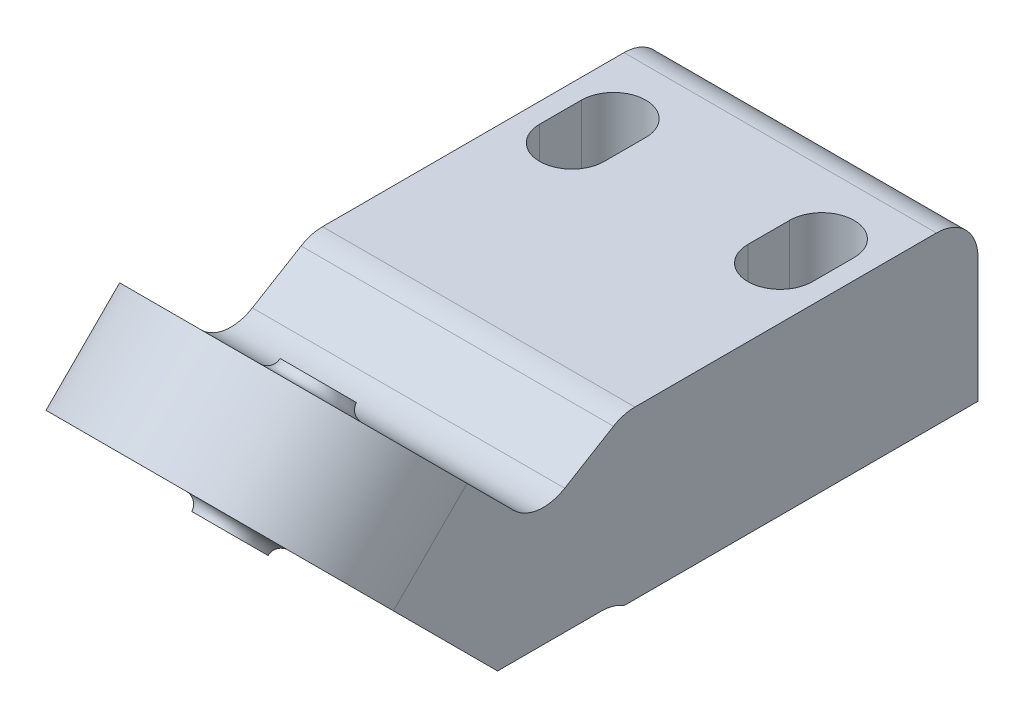
SolidWorks part; units mm, degrees
ref_plane "前视基准面" through (0, 0, 0) normal (0, 0, 1) x (1, 0, 0)
ref_plane "上视基准面" through (0, 0, 0) normal (0, 1, 0) x (1, 0, 0)
ref_plane "右视基准面" through (0, 0, 0) normal (1, 0, 0) x (0, 0, -1)
other "Configuration Table"
sketch "草图10" plane through (0, 0, 0) normal (0, 0, 1) x (1, 0, 0)
  line L0 (-7.5, 20.6821) -> (7.5, 20.6821) construction
  line L1 (-7.5, 20.6821) -> (7.5, 20.6821)
  line L2 (7.5, 20.6821) -> (7.5, 28.6821)
  line L3 (7.5, 28.6821) -> (-7.5, 28.6821)
  line L4 (-7.5, 28.6821) -> (-7.5, 20.6821)
  arc A0 (-7.5, 20.6821) -> (7.5, 20.6821) centre (0, 0) ccw construction
  dimension "D1" = 44
  dimension "D2" = 15
  dimension "D3" = 8
extrude "凸台-拉伸7" add sketch "草图10" along normal blind 11
sketch "草图11" plane through (0, 28.6821, 0) normal (0, 1, 0) x (1, 0, 0)
  line L0 (0, 3.3102) -> (0, -13.8287) construction
  line L1 (-5, -5) -> (-5, -7) construction
  line L2 (-3.45, -5) -> (-3.45, -7)
  line L3 (-6.55, -5) -> (-6.55, -7)
  line L4 (7.5, -11) -> (-7.5, -11) construction
  line L5 (5, -5) -> (5, -7) construction
  line L6 (3.45, -5) -> (3.45, -7)
  line L7 (6.55, -5) -> (6.55, -7)
  arc A0 (-3.45, -5) -> (-6.55, -5) centre (-5, -5) ccw
  arc A1 (-6.55, -7) -> (-3.45, -7) centre (-5, -7) ccw
  arc A2 (3.45, -5) -> (6.55, -5) centre (5, -5) cw
  arc A3 (6.55, -7) -> (3.45, -7) centre (5, -7) cw
  point P5 (-5, -6)
  point P14 (5, -6)
  dimension "D2" = 1.55
  dimension "D1" = 5
  dimension "D3" = 2
  dimension "D4" = 10
extrude "切除-拉伸4" cut sketch "草图11" against normal blind 11
sketch "草图12" plane through (0, 0, 11) normal (0, 0, 1) x (1, 0, 0)
  line L0 (7.5, 20.6821) -> (7.5, 28.6821) construction
  line L1 (-7.5, 28.6821) -> (7.5, 28.6821)
  line L2 (-7.5, 28.6821) -> (-7.5, 22.6821)
  line L3 (-7.5, 22.6821) -> (7.5, 22.6821)
  line L4 (7.5, 28.6821) -> (7.5, 22.6821)
  dimension "D1" = 6
extrude "凸台-拉伸8" add sketch "草图12" along normal blind 6
sketch "草图14" plane through (0, 0, 17) normal (0, 0, 1) x (1, 0, 0)
  line L0 (-7.5, 20.6821) -> (7.5, 20.6821) construction
  line L1 (0, 26) -> (-20.4245, 26) construction
  line L2 (-7.5, 26) -> (7.5, 26)
  line L3 (7.5, 26) -> (7.5, 21)
  line L4 (7.5, 20.6821) -> (7.5, 22.6821) construction
  line L5 (7.5, 21) -> (-7.5, 21)
  line L6 (-7.5, 22.6821) -> (-7.5, 20.6821) construction
  line L7 (-7.5, 21) -> (-7.5, 26)
  line L8 (-7.5, 28.6821) -> (-7.5, 22.6821) construction
  arc A0 (-7.5, 20.6821) -> (7.5, 20.6821) centre (0, 0) ccw construction
  circle A1 centre (0, 0) radius 26 construction
  dimension "D1" = 52
  dimension "D2" = 5
extrude "凸台-拉伸9" add sketch "草图14" along normal blind 4
sketch "草图17" plane through (-7.5, 0, 0) normal (-1, 0, 0) x (0, 0, 1)
  line L0 (21, 26) -> (24.5355, 29.5355)
  line L1 (21, 26) -> (17, 26) construction
  line L2 (28.0711, 26) -> (23.0711, 21)
  line L4 (24.5355, 29.5355) -> (28.0711, 26)
  line L5 (21, 26) -> (21, 21)
  line L6 (21, 21) -> (23.0711, 21)
  dimension "D1" = 135
  dimension "D2" = 5
  dimension "D3" = 5
extrude "凸台-拉伸10" add sketch "草图17" against normal blind 15
sketch "草图18" plane through (0, -1.0355, 1.0355) normal (0, -0.7071, 0.7071) x (1, 0, 0)
  line L0 (7.5, 38.234) -> (-7.5, 38.234) construction
  line L1 (7.5, 31.163) -> (7.5, 38.234) construction
  line L2 (7.5, 38.234) -> (-7.5, 38.234)
  arc A0 (-7.5, 38.234) -> (7.5, 38.234) centre (0, 38.234) cw
extrude "凸台-拉伸11" add sketch "草图18" against normal blind 5
sketch "草图19" plane through (0, -1.0355, 1.0355) normal (0, -0.7071, 0.7071) x (1, 0, 0)
  circle A0 centre (0, 38.234) radius 1.1
  dimension "D1" = 2.2
extrude "切除-拉伸5" cut sketch "草图19" against normal blind 5
sketch "草图20" plane through (0, -1.0355, 1.0355) normal (0, -0.7071, 0.7071) x (1, 0, 0)
  circle A0 centre (0, 38.234) radius 1.1 construction
  circle A1 centre (0, 38.234) radius 1.1
  circle A2 centre (0, 38.234) radius 1.5
  dimension "D1" = 3
extrude "凸台-拉伸12" add sketch "草图20" along normal blind 0.5
sketch "草图21" plane through (0, 2.5, -2.5) normal (0, 0.7071, -0.7071) x (1, 0, 0)
  circle A0 centre (0, -38.234) radius 1.1 construction
  circle A1 centre (0, -38.234) radius 1.1
  circle A2 centre (0, -38.234) radius 1.5
  dimension "D1" = 3
extrude "凸台-拉伸13" add sketch "草图21" along normal blind 0.5
fillet "圆角4" radius 0.5 2 edges at (0, 24.9393, 27.0104) (0, 30.5962, 25.5962)
chamfer "倒角1" distance 2.7 angle 59 1 edges at (0, 26, 17) first distance on face at (0, 27.3411, 17)
fillet "圆角7" radius 2 2 edges at (0, 28.6821, 17.0298) (0, 26.1852, 21.1852)
sketch "草图22" plane through (0, 0, 11) normal (0, 0, 1) x (1, 0, 0)
  line L4 (7.5, 22.6821) -> (-7.5, 22.6821)
  line L5 (-7.5, 22.6821) -> (-7.5, 20.6821)
  line L6 (-7.5, 20.6821) -> (7.5, 20.6821)
  line L7 (7.5, 20.6821) -> (7.5, 22.6821)
  line L8 (7.5, 22.6821) -> (-7.5, 22.6821)
  line L9 (-7.5, 22.6821) -> (-7.5, 20.6821)
  line L10 (-7.5, 20.6821) -> (7.5, 20.6821)
  line L11 (7.5, 20.6821) -> (7.5, 22.6821)
  dimension "D1" = 0
extrude "凸台-拉伸14" add sketch "草图22" along normal up to surface (6 mm away) up to face at (0, 21.8411, 17)
fillet "圆角8" radius 2 1 edges at (0, 21, 17)
fillet "圆角9" radius 2 1 edges at (0, 28.6821, 0)
